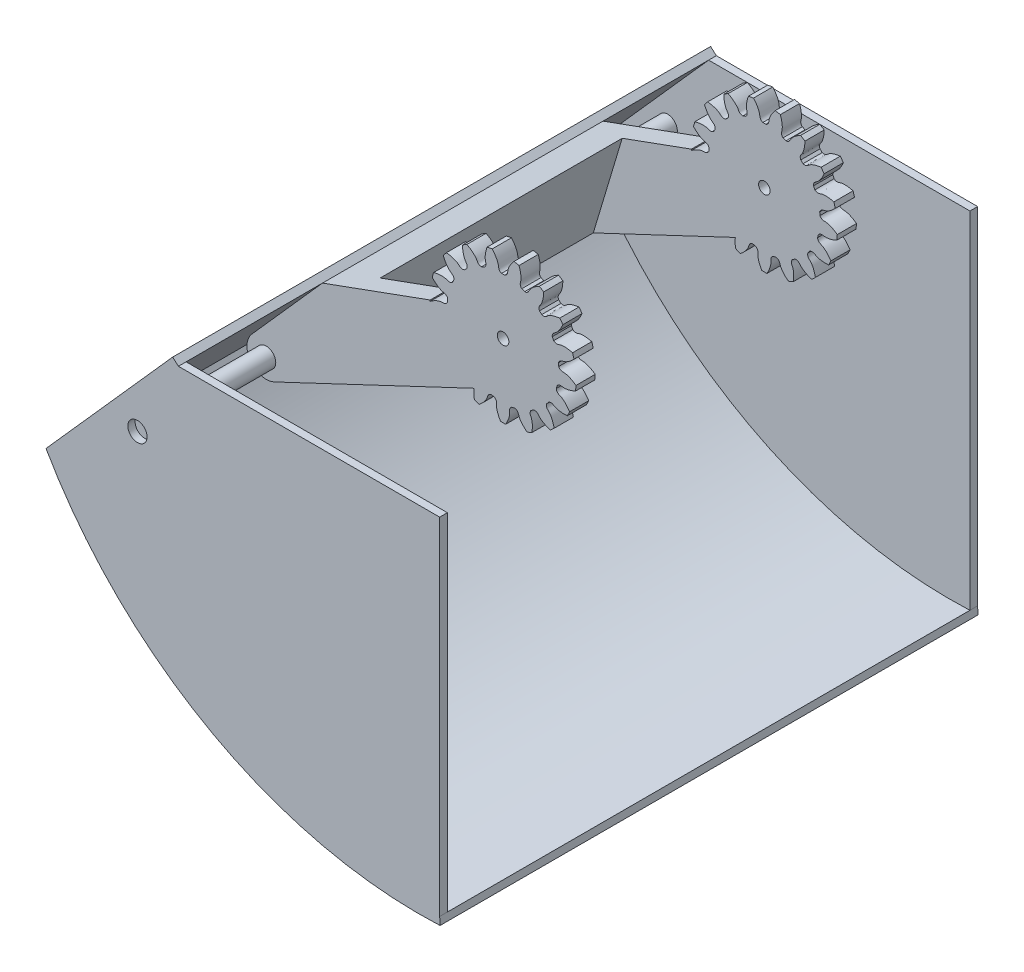
SolidWorks part; units mm, degrees
note: '?' marks a value the reader was unsure of.
ref_plane "前视基准面" through (0, 0, 0) normal (0, 0, 1) x (1, 0, 0)
ref_plane "上视基准面" through (0, 0, 0) normal (0, 1, 0) x (1, 0, 0)
ref_plane "右视基准面" through (0, 0, 0) normal (1, 0, 0) x (0, 0, -1)
sketch "草图1" plane through (0, 0, 0) normal (0, 0, 1) x (1, 0, 0)
  circle A0 centre (0, 0) radius 19
extrude "凸台-拉伸1" add sketch "草图1" along normal blind 5
ref_axis "基准轴1" through (0, 0, -1.5) along (0, 0, 1)?
sketch "草图2" plane through (0, 0, 0) normal (0, 0, 1) x (1, 0, 0)
  line L0 (0, 0) -> (0, 19) construction
  circle A0 centre (0, 0) radius 19 construction
  arc A1 (0.4034, 14.4944) -> (-0.4034, 14.4944) centre (0, 0) ccw
  arc A2 (6.2313, 21.4814) -> (-6.2313, 21.4814) centre (0, 0) ccw
  spline S0 degree 3 poles (0.4034, 14.4944) (1.2558, 14.8496) (1.1324, 15.5096) (1.2766, 16.1296) (1.29, 16.1823) (1.306, 16.2408) (1.3251, 16.3052) (1.3474, 16.3752) (1.3731, 16.4508) (1.4025, 16.5319) (1.4359, 16.6184) (1.4733, 16.7101) (1.5152, 16.8068) (1.5616, 16.9086) (1.6128, 17.0151) (1.669, 17.1264) (1.7304, 17.2421) (1.7972, 17.3621) (1.8696, 17.4863) (1.9478, 17.6145) (2.032, 17.7465) (2.1224, 17.8821) (2.2191, 18.0211) (2.3223, 18.1634) (2.4322, 18.3086) (2.5489, 18.4566) (2.6727, 18.6072) (2.8035, 18.7601) (2.9417, 18.9152) (3.0873, 19.0722) (3.2404, 19.2308) (3.4012, 19.3908) (3.5698, 19.552) (3.7462, 19.7141) (3.9307, 19.8769) (4.1233, 20.0401) (4.324, 20.2035) (4.533, 20.3667) (4.7503, 20.5295) (4.9761, 20.6917) (5.2103, 20.853) (5.453, 21.0131) (5.7916, 21.2269) (6.0532, 21.3811) (6.2313, 21.4814) knots 0 0 0 0 0.193883 0.199024 0.204851 0.211363 0.21856 0.226443 0.235011 0.244265 0.254205 0.264829 0.27614 0.288136 0.300817 0.314184 0.328236 0.342973 0.358397 0.374505 0.391299 0.408779 0.426944 0.445795 0.465331 0.485552 0.506459 0.528051 0.550329 0.573293 0.596941 0.621276 0.646296 0.672001 0.698392 0.725468 0.753229 0.781677 0.810809 0.840627 0.871131 0.90232 0.934195 1 1 1 1
  spline S1 degree 3 poles (-0.4034, 14.4944) (-1.2558, 14.8496) (-1.1324, 15.5096) (-1.2766, 16.1296) (-1.29, 16.1823) (-1.306, 16.2408) (-1.3251, 16.3052) (-1.3474, 16.3752) (-1.3731, 16.4508) (-1.4025, 16.5319) (-1.4359, 16.6184) (-1.4733, 16.7101) (-1.5152, 16.8068) (-1.5616, 16.9086) (-1.6128, 17.0151) (-1.669, 17.1264) (-1.7304, 17.2421) (-1.7972, 17.3621) (-1.8696, 17.4863) (-1.9478, 17.6145) (-2.032, 17.7465) (-2.1224, 17.8821) (-2.2191, 18.0211) (-2.3223, 18.1634) (-2.4322, 18.3086) (-2.5489, 18.4566) (-2.6727, 18.6072) (-2.8035, 18.7601) (-2.9417, 18.9152) (-3.0873, 19.0722) (-3.2404, 19.2308) (-3.4012, 19.3908) (-3.5698, 19.552) (-3.7462, 19.7141) (-3.9307, 19.8769) (-4.1233, 20.0401) (-4.324, 20.2035) (-4.533, 20.3667) (-4.7503, 20.5295) (-4.9761, 20.6917) (-5.2103, 20.853) (-5.453, 21.0131) (-5.7916, 21.2269) (-6.0532, 21.3811) (-6.2313, 21.4814) knots 0 0 0 0 0.193883 0.199024 0.204851 0.211363 0.21856 0.226443 0.235011 0.244265 0.254205 0.264829 0.27614 0.288136 0.300817 0.314184 0.328236 0.342973 0.358397 0.374505 0.391299 0.408779 0.426944 0.445795 0.465331 0.485552 0.506459 0.528051 0.550329 0.573293 0.596941 0.621276 0.646296 0.672001 0.698392 0.725468 0.753229 0.781677 0.810809 0.840627 0.871131 0.90232 0.934195 1 1 1 1
extrude "切除-拉伸1" cut sketch "草图2" along normal through all
pattern_circular "阵列(圆周)1" count 17 over 360 about axis through (0, 0, -1.5) along (0, 0, 1) of "切除-拉伸1"
sketch "草图3" plane through (0, 0, 0) normal (0, 0, 1) x (1, 0, 0)
  circle A0 centre (0, 0) radius 17 construction
  dimension "Dn" = 34
sketch "草图4" plane through (0, 0, 5) normal (0, 0, 1) x (1, 0, 0)
  circle A0 centre (0, 0) radius 1.5
  dimension "D1" = 3
extrude "切除-拉伸2" cut sketch "草图4" against normal up to next
sketch "草图5" plane through (0, 0, 5) normal (0, 0, 1) x (1, 0, 0)
  line L0 (-18.983, -0.8027) -> (-47, -11)
  line L1 (-47, -11) -> (-81.6624, -50)
  line L2 (-81.6624, -50) -> (-7.5441, -14.9851)
  line L3 (0, 0) -> (0, 43.3356) construction
  line L4 (-47, -11) -> (-47, -47.1311) construction
  arc A0 (-18.9691, -1.0834) -> (-18.8452, -2.4206) centre (0, 0) ccw construction
  arc A1 (-18.983, -0.8027) -> (-18.8452, -2.4206) centre (0, 0) ccw
  arc A34 (-4.8598, 13.6613) -> (-5.6121, 13.3699) centre (0, 0) ccw
  arc A35 (-9.4251, 16.4975) -> (-10.5668, 15.7906) centre (0, 0) ccw
  arc A36 (-9.4667, 10.9832) -> (-10.0629, 10.4397) centre (0, 0) ccw
  arc A37 (-14.7482, 11.9787) -> (-15.5575, 10.9071) centre (0, 0) ccw
  arc A38 (-12.795, 6.8218) -> (-13.1546, 6.0996) centre (0, 0) ccw
  arc A39 (-18.0795, 5.8422) -> (-18.447, 4.5505) centre (0, 0) ccw
  arc A40 (-14.3953, 1.739) -> (-14.4698, 0.9357) centre (0, 0) ccw
  arc A41 (-18.9691, -1.0834) -> (-18.8452, -2.4206) centre (0, 0) ccw
  arc A42 (-14.0515, -3.5786) -> (-13.8307, -4.3546) centre (0, 0) ccw
  arc A43 (-17.2968, -7.8627) -> (-16.6982, -9.0648) centre (0, 0) ccw
  arc A44 (-11.8099, -8.4129) -> (-11.3237, -9.0567) centre (0, 0) ccw
  arc A45 (-13.2884, -13.5801) -> (-12.296, -14.4847) centre (0, 0) ccw
  arc A46 (-7.9733, -12.111) -> (-7.2873, -12.5357) centre (0, 0) ccw
  arc A47 (-7.4854, -17.4634) -> (-6.2332, -17.9485) centre (0, 0) ccw
  arc A48 (-3.0599, -14.1735) -> (-2.2668, -14.3217) centre (0, 0) ccw
  arc A49 (-0.6714, -18.9881) -> (0.6714, -18.9881) centre (0, 0) ccw
  arc A50 (2.2668, -14.3217) -> (3.0599, -14.1735) centre (0, 0) ccw
  arc A51 (6.2332, -17.9485) -> (7.4854, -17.4634) centre (0, 0) ccw
  arc A52 (7.2873, -12.5357) -> (7.9733, -12.111) centre (0, 0) ccw
  arc A53 (12.296, -14.4847) -> (13.2884, -13.5801) centre (0, 0) ccw
  arc A54 (11.3237, -9.0567) -> (11.8099, -8.4129) centre (0, 0) ccw
  arc A55 (16.6982, -9.0648) -> (17.2968, -7.8627) centre (0, 0) ccw
  arc A56 (13.8307, -4.3546) -> (14.0515, -3.5786) centre (0, 0) ccw
  arc A57 (18.8452, -2.4206) -> (18.9691, -1.0834) centre (0, 0) ccw
  arc A58 (14.4698, 0.9357) -> (14.3953, 1.739) centre (0, 0) ccw
  arc A59 (18.447, 4.5505) -> (18.0795, 5.8422) centre (0, 0) ccw
  arc A60 (13.1546, 6.0996) -> (12.795, 6.8218) centre (0, 0) ccw
  arc A61 (15.5575, 10.9071) -> (14.7482, 11.9787) centre (0, 0) ccw
  arc A62 (10.0629, 10.4397) -> (9.4667, 10.9832) centre (0, 0) ccw
  arc A63 (10.5668, 15.7906) -> (9.4251, 16.4975) centre (0, 0) ccw
  arc A64 (5.6121, 13.3699) -> (4.8598, 13.6613) centre (0, 0) ccw
  arc A65 (4.1491, 18.5414) -> (2.8291, 18.7882) centre (0, 0) ccw
  arc A66 (0.4034, 14.4944) -> (-0.4034, 14.4944) centre (0, 0) ccw
  arc A67 (-2.8291, 18.7882) -> (-4.1491, 18.5414) centre (0, 0) ccw
  arc A76 (-14.0515, -3.5786) -> (-13.8307, -4.3546) centre (0, 0) ccw
  arc A77 (-17.2968, -7.8627) -> (-16.6982, -9.0648) centre (0, 0) ccw
  arc A78 (-11.8099, -8.4129) -> (-11.3237, -9.0567) centre (0, 0) ccw
  arc A79 (-13.2884, -13.5801) -> (-12.296, -14.4847) centre (0, 0) ccw
  arc A80 (-7.9733, -12.111) -> (-7.2873, -12.5357) centre (0, 0) ccw
  spline S1 degree 3 poles (-7.4854, -17.4634) (-7.5096, -17.32) (-7.5487, -17.0538) (-7.5886, -16.6719) (-7.6106, -16.3274) (-7.6183, -16.008) (-7.6136, -15.714) (-7.5986, -15.446) (-7.5788, -15.2392) (-7.5553, -15.0543) (-7.5342, -14.9196) (-7.5105, -14.7941) (-7.4928, -14.7096) (-7.4749, -14.6318) (-7.4569, -14.5605) (-7.4345, -14.4783) (-7.4122, -14.4049) (-7.202, -13.7827) (-6.7497, -13.2865) (-7.2873, -12.5357) knots 0.467653 0.467653 0.467653 0.467653 0.514448 0.554205 0.591221 0.625495 0.657027 0.685816 0.711864 0.72386 0.745795 0.755735 0.764989 0.773557 0.78144 0.788637 0.800976 0.806117 1 1 1 1 construction
  spline S36 degree 3 poles (801.6528, 603.553) (-19.7252, -7.542) (-3.7936, 9.8487) (-7.0285, 14.596) (-7.0736, 14.658) (-7.1257, 14.7254) (-7.1718, 14.7827) (-7.243, 14.8676) (-7.3458, 14.9828) (-7.4879, 15.1299) (-7.6543, 15.2888) (-7.8461, 15.4578) (-8.0643, 15.6352) (-8.3098, 15.8191) (-8.5836, 16.0075) (-8.8863, 16.1985) (-30.7559, 28.8047) (-98.5587, -42.3055) (899.0002, 434.536) knots -1.169641 -1.169641 -1.169641 -1.169641 0.661536 0.666677 0.679016 0.686213 0.694096 0.702664 0.721858 0.743793 0.76847 0.795889 0.82605 0.858952 0.894597 0.932984 0.974112 9.016656 9.016656 9.016656 9.016656 only from (-5.6121, 13.3699) to (-9.4251, 16.4975)
  spline S37 degree 3 poles (-789.8845, -610.8384) (79.969, 69.9323) (-12.5204, 39.6369) (-10.5228, 14.9936) (-10.4812, 14.651) (-10.43, 14.3355) (-10.3714, 14.0475) (-10.3075, 13.7868) (-10.25, 13.5872) (-10.1929, 13.4097) (-10.1474, 13.2812) (-10.101, 13.1621) (-10.0681, 13.0824) (-10.0362, 13.0091) (-10.0055, 12.9424) (-9.9683, 12.8657) (-9.9329, 12.7977) (-7.1253, 7.786) (15.5424, 14.2951) (-897.5321, -448.5461) knots -7.831656 -7.831656 -7.831656 -7.831656 0.046795 0.086552 0.123568 0.157842 0.189373 0.218163 0.244211 0.256207 0.278142 0.288082 0.297336 0.305904 0.313787 0.320984 0.333323 0.338464 2.169591 2.169591 2.169591 2.169591 only from (-10.5668, 15.7906) to (-9.4667, 10.9832)
  spline S38 degree 3 poles (529.4905, 852.3868) (-15.6687, -14.1583) (-7.0952, 7.8132) (-11.8266, 11.0714) (-11.8911, 11.1129) (-11.964, 11.157) (-12.0276, 11.1937) (-12.1246, 11.2471) (-12.2622, 11.3174) (-12.4478, 11.4032) (-12.6604, 11.4913) (-12.9003, 11.5797) (-13.1678, 11.6663) (-13.4632, 11.749) (-13.7866, 11.8258) (-14.1378, 11.8946) (-39.0844, 15.7493) (-76.6207, -75.0522) (681.3202, 729.9491) knots -1.169641 -1.169641 -1.169641 -1.169641 0.661536 0.666677 0.679016 0.686213 0.694096 0.702664 0.721858 0.743793 0.76847 0.795889 0.82605 0.858952 0.894597 0.932984 0.974112 9.016656 9.016656 9.016656 9.016656 only from (-10.0629, 10.4397) to (-14.7482, 11.9787)
  spline S39 degree 3 poles (-515.8851, -854.929) (49.3064, 94.0981) (-25.9934, 32.4374) (-15.2285, 10.1798) (-15.066, 9.8754) (-14.9043, 9.5997) (-14.7456, 9.3523) (-14.5918, 9.1323) (-14.466, 8.9669) (-14.3487, 8.8221) (-14.2599, 8.7187) (-14.1736, 8.6244) (-14.1141, 8.5619) (-14.0579, 8.5052) (-14.0051, 8.454) (-13.9428, 8.3959) (-13.8852, 8.3453) (-9.4567, 4.6863) (9.3288, 18.9444) (-674.8902, -742.4828) knots -7.831656 -7.831656 -7.831656 -7.831656 0.046795 0.086552 0.123568 0.157842 0.189373 0.218163 0.244211 0.256207 0.278142 0.288082 0.297336 0.305904 0.313787 0.320984 0.333323 0.338464 2.169591 2.169591 2.169591 2.169591 only from (-15.5575, 10.9071) to (-12.795, 6.8218)
  spline S40 degree 3 poles (185.8176, 986.101) (-9.496, -18.8624) (-9.4385, 4.7225) (-15.0274, 6.0515) (-15.1025, 6.0669) (-15.1864, 6.0817) (-15.2591, 6.0929) (-15.3688, 6.1077) (-15.5225, 6.1236) (-15.7266, 6.1365) (-15.9566, 6.1418) (-16.2122, 6.1376) (-16.493, 6.1217) (-16.7983, 6.0922) (-17.1276, 6.047) (-17.4799, 5.9842) (-42.1345, 0.5668) (-44.3347, -97.6627) (371.6241, 926.7785) knots -1.169641 -1.169641 -1.169641 -1.169641 0.661536 0.666677 0.679016 0.686213 0.694096 0.702664 0.721858 0.743793 0.76847 0.795889 0.82605 0.858952 0.894597 0.932984 0.974112 9.016656 9.016656 9.016656 9.016656 only from (-13.1546, 6.0996) to (-18.0795, 5.8422)
  spline S41 degree 3 poles (-172.2126, -983.5568) (11.9847, 105.5554) (-35.9559, 20.8571) (-17.8776, 3.9912) (-17.616, 3.7661) (-17.3657, 3.5674) (-17.1283, 3.394) (-16.9054, 3.2444) (-16.7284, 3.1357) (-16.5667, 3.043) (-16.4465, 2.9787) (-16.332, 2.9219) (-16.2539, 2.8852) (-16.181, 2.8525) (-16.1134, 2.8239) (-16.0342, 2.7923) (-15.9623, 2.7658) (-10.511, 0.9536) (1.8554, 21.035) (-361.1007, -936.143) knots -7.831656 -7.831656 -7.831656 -7.831656 0.046795 0.086552 0.123568 0.157842 0.189373 0.218163 0.244211 0.256207 0.278142 0.288082 0.297336 0.305904 0.313787 0.320984 0.333323 0.338464 2.169591 2.169591 2.169591 2.169591 only from (-18.447, 4.5505) to (-14.3953, 1.739)
  spline S42 degree 3 poles (-182.9511, 986.6369) (-2.0409, -21.019) (-10.5071, 0.994) (-16.1987, 0.2143) (-16.2743, 0.2016) (-16.3579, 0.185) (-16.4297, 0.1693) (-16.5374, 0.1434) (-16.6864, 0.1027) (-16.8814, 0.041) (-17.0978, -0.0371) (-17.3346, -0.1334) (-17.5907, -0.2496) (-17.8647, -0.3875) (-18.1554, -0.5486) (-18.4613, -0.7344) (-39.494, -14.6922) (-6.061, -107.0833) (11.7382, 998.4413) knots -1.169641 -1.169641 -1.169641 -1.169641 0.661536 0.666677 0.679016 0.686213 0.694096 0.702664 0.721858 0.743793 0.76847 0.795889 0.82605 0.858952 0.894597 0.932984 0.974112 9.016656 9.016656 9.016656 9.016656 only from (-14.4698, 0.9357) to (-18.9691, -1.0834)
  spline S43 degree 3 poles (755.9193, -3926.2535) (-1.4249, 230.148) (-53.2365, 11.3382) (-18.1121, -2.7364) (-17.7869, -2.8519) (-17.4817, -2.9467) (-17.1977, -3.0226) (-16.9358, -3.0816) (-16.7315, -3.1191) (-16.5473, -3.147) (-16.4119, -3.1636) (-16.2846, -3.1752) (-16.1986, -3.1813) (-16.1188, -3.1853) (-16.0454, -3.1876) (-15.9602, -3.1885) (-15.8835, -3.1872) (-6.8836, -2.7489) (-1.4385, 54.3405) (17.9437, -4002.7644) knots -12.051564 -12.051564 -12.051564 -12.051564 0.046795 0.086552 0.123568 0.157842 0.189373 0.218163 0.244211 0.256207 0.278142 0.288082 0.297336 0.305904 0.313787 0.320984 0.333323 0.338464 3.220589 3.220589 3.220589 3.220589 only from (-18.8452, -2.4206) to (-14.0515, -3.5786)
  spline S44 degree 3 poles (-2091.9835, 3412.7558) (27.3841, -46.9593) (-7.2996, -1.2865) (-15.1823, -5.6518) (-15.2482, -5.691) (-15.3201, -5.7366) (-15.3814, -5.7772) (-15.4724, -5.8403) (-15.5967, -5.932) (-15.7562, -6.06) (-15.9298, -6.211) (-16.1158, -6.3864) (-16.3126, -6.5872) (-16.5184, -6.8148) (-16.7313, -7.07) (-16.9493, -7.3538) (-39.2418, -38.8919) (124.1972, -196.1218) (-1429.0442, 3734.2026) knots -2.220614 -2.220614 -2.220614 -2.220614 0.661536 0.666677 0.679016 0.686213 0.694096 0.702664 0.721858 0.743793 0.76847 0.795889 0.82605 0.858952 0.894597 0.932984 0.974112 13.321347 13.321347 13.321347 13.321347 only from (-13.8307, -4.3546) to (-17.2968, -7.8627)
  spline S45 degree 3 poles (2123.2001, -3388.0528) (-84.4678, 214.0919) (-53.7373, -8.6587) (-15.9006, -9.0945) (-15.5556, -9.0847) (-15.2368, -9.0628) (-14.9445, -9.031) (-14.679, -8.9914) (-14.4749, -8.9526) (-14.293, -8.9121) (-14.1608, -8.8786) (-14.038, -8.8435) (-13.9555, -8.8181) (-13.8797, -8.793) (-13.8104, -8.7686) (-13.7306, -8.7387) (-13.6596, -8.7097) (-5.4257, -5.05) (-20.9714, 50.1513) (1462.6972, -3725.9846) knots -12.051564 -12.051564 -12.051564 -12.051564 0.046795 0.086552 0.123568 0.157842 0.189373 0.218163 0.244211 0.256207 0.278142 0.288082 0.297336 0.305904 0.313787 0.320984 0.333323 0.338464 3.220589 3.220589 3.220589 3.220589 only from (-16.6982, -9.0648) to (-11.8099, -8.4129)
  spline S46 degree 3 poles (-3183.5461, 2426.5884) (42.4986, -33.896) (-6.342, -3.8366) (-12.1154, -10.7546) (-12.1627, -10.815) (-12.2133, -10.8835) (-12.2557, -10.9435) (-12.3179, -11.0352) (-12.4006, -11.1656) (-12.5031, -11.3426) (-12.6104, -11.5461) (-12.7206, -11.7768) (-12.8315, -12.0352) (-12.9411, -12.3217) (-13.0474, -12.6366) (-13.1483, -12.98) (-22.5426, -50.4414) (186.6578, -138.0129) (-2681.4936, 2965.8099) knots -2.220614 -2.220614 -2.220614 -2.220614 0.661536 0.666677 0.679016 0.686213 0.694096 0.702664 0.721858 0.743793 0.76847 0.795889 0.82605 0.858952 0.894597 0.932984 0.974112 13.321347 13.321347 13.321347 13.321347 only from (-11.3237, -9.0567) to (-13.2884, -13.5801)
  spline S47 degree 3 poles (3203.731, -2392.2768) (-156.1027, 169.1214) (-46.9807, -27.4862) (-11.5415, -14.2243) (-11.2234, -14.0905) (-10.934, -13.955) (-10.6729, -13.8198) (-10.4397, -13.6869) (-10.2635, -13.577) (-10.1084, -13.4735) (-9.9973, -13.3946) (-9.8954, -13.3174) (-9.8277, -13.2639) (-9.766, -13.2132) (-9.7102, -13.1654) (-9.6466, -13.1086) (-9.5908, -13.056) (-3.2351, -6.6689) (-37.672, 39.1889) (2709.9054, -2945.99) knots -12.051564 -12.051564 -12.051564 -12.051564 0.046795 0.086552 0.123568 0.157842 0.189373 0.218163 0.244211 0.256207 0.278142 0.288082 0.297336 0.305904 0.313787 0.320984 0.333323 0.338464 3.220589 3.220589 3.220589 3.220589 only from (-12.296, -14.4847) to (-7.9733, -12.111)
  spline S48 degree 3 poles (-3845.1532, 1112.6968) (51.8734, -16.2548) (-4.5278, -5.8685) (-7.4122, -14.4049) (-7.4345, -14.4783) (-7.4569, -14.5605) (-7.4749, -14.6318) (-7.4997, -14.7397) (-7.5297, -14.8912) (-7.5614, -15.0933) (-7.5879, -15.3218) (-7.6073, -15.5767) (-7.6174, -15.8578) (-7.6161, -16.1645) (-7.6015, -16.4966) (-7.5715, -16.8532) (-2.7988, -55.1785) (223.9092, -61.2646) (-3571.7924, 1796.8681) knots -2.220614 -2.220614 -2.220614 -2.220614 0.661536 0.666677 0.679016 0.686213 0.694096 0.702664 0.721858 0.743793 0.76847 0.795889 0.82605 0.858952 0.894597 0.932984 0.974112 13.321347 13.321347 13.321347 13.321347 only from (-7.2873, -12.5357) to (-7.4854, -17.4634)
  spline S49 degree 3 poles (963.4713, -262.2291) (-103.9993, 21.673) (-24.0857, -33.8781) (-5.6237, -17.433) (-5.3754, -17.1934) (-5.1545, -16.9624) (-4.9599, -16.7421) (-4.7904, -16.5339) (-4.6658, -16.3677) (-4.5586, -16.2153) (-4.4835, -16.1015) (-4.4164, -15.9927) (-4.3726, -15.9184) (-4.3334, -15.8488) (-4.2986, -15.7841) (-4.2598, -15.7082) (-4.2268, -15.639) (-1.9194, -10.3782) (-20.7741, 3.7883) (898.8314, -445.9367) knots -7.831656 -7.831656 -7.831656 -7.831656 0.046795 0.086552 0.123568 0.157842 0.189373 0.218163 0.244211 0.256207 0.278142 0.288082 0.297336 0.305904 0.313787 0.320984 0.333323 0.338464 2.169591 2.169591 2.169591 2.169591 only from (-6.2332, -17.9485) to (-3.0599, -14.1735)
  spline S50 degree 3 poles (-999.3086, -91.1352) (20.741, -3.9716) (-1.9593, -10.3706) (-1.7081, -16.1098) (-1.7023, -16.1863) (-1.6935, -16.271) (-1.6845, -16.344) (-1.6687, -16.4536) (-1.6419, -16.6057) (-1.5985, -16.8056) (-1.5407, -17.0283) (-1.4666, -17.273) (-1.3745, -17.5386) (-1.2625, -17.8243) (-1.129, -18.1286) (-0.9721, -18.4503) (10.9855, -40.6811) (106.0673, -15.9155) (-993.0991, 103.8126) knots -1.169641 -1.169641 -1.169641 -1.169641 0.661536 0.666677 0.679016 0.686213 0.694096 0.702664 0.721858 0.743793 0.76847 0.795889 0.82605 0.858952 0.894597 0.932984 0.974112 9.016656 9.016656 9.016656 9.016656 only from (-2.2668, -14.3217) to (-0.6714, -18.9881)
  spline S51 degree 3 poles (993.1383, 103.5246) (-104.8057, -17.3594) (-10.2211, -40.2911) (1.0535, -18.2873) (1.1985, -17.9742) (1.3211, -17.679) (1.4229, -17.4032) (1.5058, -17.1479) (1.562, -16.9479) (1.6068, -16.767) (1.6358, -16.6338) (1.6591, -16.5081) (1.6731, -16.423) (1.6845, -16.344) (1.6935, -16.271) (1.7023, -16.1863) (1.7081, -16.1098) (1.9593, -10.3707) (-20.7398, -3.9719) (999.2263, -91.1282) knots -7.831656 -7.831656 -7.831656 -7.831656 0.046795 0.086552 0.123568 0.157842 0.189373 0.218163 0.244211 0.256207 0.278142 0.288082 0.297336 0.305904 0.313787 0.320984 0.333323 0.338464 2.169591 2.169591 2.169591 2.169591 only from (0.6714, -18.9881) to (2.2668, -14.3217)
  spline S52 degree 3 poles (-898.9057, -445.973) (20.7751, 3.7891) (1.9193, -10.3781) (4.2268, -15.639) (4.2598, -15.7082) (4.2986, -15.7841) (4.3334, -15.8488) (4.3877, -15.9453) (4.4676, -16.0775) (4.5803, -16.2481) (4.7147, -16.4349) (4.8721, -16.6364) (5.054, -16.8508) (5.2616, -17.0767) (5.4961, -17.3122) (5.7585, -17.5556) (24.9393, -33.9656) (104.6541, 23.4751) (-963.5388, -261.9464) knots -1.169641 -1.169641 -1.169641 -1.169641 0.661536 0.666677 0.679016 0.686213 0.694096 0.702664 0.721858 0.743793 0.76847 0.795889 0.82605 0.858952 0.894597 0.932984 0.974112 9.016656 9.016656 9.016656 9.016656 only from (3.0599, -14.1735) to (6.2332, -17.9485)
  spline S53 degree 3 poles (888.6765, 455.2968) (-91.4574, -54.0473) (5.0239, -41.2626) (7.5886, -16.6719) (7.6106, -16.3274) (7.6183, -16.008) (7.6136, -15.714) (7.5986, -15.446) (7.5788, -15.2392) (7.5553, -15.0543) (7.5342, -14.9196) (7.5105, -14.7941) (7.4928, -14.7096) (7.4749, -14.6318) (7.4569, -14.5605) (7.4345, -14.4783) (7.4122, -14.4049) (5.5733, -8.9627) (-17.9045, -11.1958) (964.67, 275.9876) knots -7.831656 -7.831656 -7.831656 -7.831656 0.046795 0.086552 0.123568 0.157842 0.189373 0.218163 0.244211 0.256207 0.278142 0.288082 0.297336 0.305904 0.313787 0.320984 0.333323 0.338464 2.169591 2.169591 2.169591 2.169591 only from (7.4854, -17.4634) to (7.2873, -12.5357)
  spline S54 degree 3 poles (-677.1006, -740.5796) (18.0035, 11.0381) (5.5387, -8.9839) (9.5908, -13.056) (9.6466, -13.1086) (9.7102, -13.1654) (9.766, -13.2132) (9.8515, -13.2835) (9.9738, -13.3779) (10.1406, -13.4963) (10.3333, -13.622) (10.5529, -13.7529) (10.7999, -13.8872) (11.0751, -14.0228) (11.3788, -14.1577) (11.7115, -14.2899) (35.525, -22.6629) (89.1069, 59.6953) (-803.8472, -592.3281) knots -1.169641 -1.169641 -1.169641 -1.169641 0.661536 0.666677 0.679016 0.686213 0.694096 0.702664 0.721858 0.743793 0.76847 0.795889 0.82605 0.858952 0.894597 0.932984 0.974112 9.016656 9.016656 9.016656 9.016656 only from (7.9733, -12.111) to (12.296, -14.4847)
  spline S55 degree 3 poles (664.194, 745.5786) (-65.7574, -83.4359) (19.5905, -36.6614) (13.0987, -12.8047) (12.9948, -12.4756) (12.8866, -12.1749) (12.776, -11.9025) (12.6653, -11.658) (12.5721, -11.4724) (12.4833, -11.3085) (12.415, -11.1905) (12.3475, -11.082) (12.3005, -11.0096) (12.2557, -10.9435) (12.2133, -10.8835) (12.1627, -10.815) (12.1154, -10.7546) (8.4346, -6.3441) (-12.651, -16.9076) (799.8298, 605.8298) knots -7.831656 -7.831656 -7.831656 -7.831656 0.046795 0.086552 0.123568 0.157842 0.189373 0.218163 0.244211 0.256207 0.278142 0.288082 0.297336 0.305904 0.313787 0.320984 0.333323 0.338464 2.169591 2.169591 2.169591 2.169591 only from (13.2884, -13.5801) to (11.3237, -9.0567)
  spline S56 degree 3 poles (-363.8493, -935.1669) (12.8003, 16.7963) (8.4101, -6.3764) (13.6596, -8.7097) (13.7306, -8.7387) (13.8104, -8.7686) (13.8797, -8.793) (13.9849, -8.8277) (14.133, -8.8716) (14.3312, -8.9218) (14.5563, -8.9693) (14.8084, -9.0121) (15.0873, -9.048) (15.3929, -9.0751) (15.7248, -9.0912) (16.0827, -9.0942) (41.3129, -8.2994) (61.5253, 87.8533) (-535.5916, -842.7126) knots -1.169641 -1.169641 -1.169641 -1.169641 0.661536 0.666677 0.679016 0.686213 0.694096 0.702664 0.721858 0.743793 0.76847 0.795889 0.82605 0.858952 0.894597 0.932984 0.974112 9.016656 9.016656 9.016656 9.016656 only from (11.8099, -8.4129) to (16.6982, -9.0648)
  spline S57 degree 3 poles (350.0084, 935.1659) (-31.1764, -101.5559) (31.5112, -27.1089) (16.8398, -7.2083) (16.624, -6.9389) (16.4145, -6.6976) (16.213, -6.4835) (16.0214, -6.2956) (15.8674, -6.1561) (15.7255, -6.0353) (15.6191, -5.95) (15.517, -5.8732) (15.447, -5.8227) (15.3814, -5.7772) (15.3201, -5.7366) (15.2482, -5.691) (15.1823, -5.6518) (10.1568, -2.8688) (-5.689, -20.336) (526.9681, 853.8513) knots -7.831656 -7.831656 -7.831656 -7.831656 0.046795 0.086552 0.123568 0.157842 0.189373 0.218163 0.244211 0.256207 0.278142 0.288082 0.297336 0.305904 0.313787 0.320984 0.333323 0.338464 2.169591 2.169591 2.169591 2.169591 only from (17.2968, -7.8627) to (13.8307, -4.3546)
  spline S58 degree 3 poles (-1.4581, -1003.4547) (5.8684, 20.2861) (10.1456, -2.9078) (15.8835, -3.1872) (15.9602, -3.1885) (16.0454, -3.1876) (16.1188, -3.1853) (16.2294, -3.1797) (16.3834, -3.1671) (16.5864, -3.1423) (16.8135, -3.1053) (17.0639, -3.0541) (17.337, -2.9869) (17.6317, -2.9017) (17.9471, -2.7968) (18.2819, -2.6704) (41.5212, 7.185) (25.6343, 104.1463) (-195.0014, -979.2841) knots -1.169641 -1.169641 -1.169641 -1.169641 0.661536 0.666677 0.679016 0.686213 0.694096 0.702664 0.721858 0.743793 0.76847 0.795889 0.82605 0.858952 0.894597 0.932984 0.974112 9.016656 9.016656 9.016656 9.016656 only from (14.0515, -3.5786) to (18.8452, -2.4206)
  spline S59 degree 3 poles (-11.4478, 998.4538) (7.6151, -105.9603) (39.1762, -13.8951) (18.3065, -0.6383) (18.0081, -0.465) (17.7255, -0.3157) (17.4603, -0.1889) (17.2137, -0.0828) (17.0198, -0.0085) (16.8438, 0.0529) (16.7138, 0.094) (16.5908, 0.1288) (16.5073, 0.1506) (16.4297, 0.1693) (16.3579, 0.185) (16.2743, 0.2016) (16.1987, 0.2143) (10.5073, 0.994) (2.0414, -21.0178) (182.9364, 986.5555) knots -7.831656 -7.831656 -7.831656 -7.831656 0.046795 0.086552 0.123568 0.157842 0.189373 0.218163 0.244211 0.256207 0.278142 0.288082 0.297336 0.305904 0.313787 0.320984 0.333323 0.338464 2.169591 2.169591 2.169591 2.169591 only from (18.9691, -1.0834) to (14.4698, 0.9357)
  spline S60 degree 3 poles (361.13, -936.2203) (-1.8561, 21.0361) (10.5109, 0.9536) (15.9623, 2.7658) (16.0342, 2.7923) (16.1134, 2.8239) (16.181, 2.8525) (16.2821, 2.8978) (16.4211, 2.9651) (16.6015, 3.0616) (16.7998, 3.1782) (17.0149, 3.3163) (17.2453, 3.4776) (17.4893, 3.6635) (17.7455, 3.8753) (18.012, 4.1141) (36.1218, 21.699) (-13.7187, 106.3737) (171.9248, -983.5979) knots -1.169641 -1.169641 -1.169641 -1.169641 0.661536 0.666677 0.679016 0.686213 0.694096 0.702664 0.721858 0.743793 0.76847 0.795889 0.82605 0.858952 0.894597 0.932984 0.974112 9.016656 9.016656 9.016656 9.016656 only from (14.3953, 1.739) to (18.447, 4.5505)
  spline S61 degree 3 poles (-371.3578, 926.8951) (45.3782, -96.0541) (41.5502, 1.1953) (17.3009, 6.0179) (16.96, 6.0716) (16.6426, 6.1088) (16.3495, 6.1312) (16.0812, 6.1411) (15.8735, 6.1404) (15.6872, 6.134) (15.5512, 6.1254) (15.4239, 6.1134) (15.3382, 6.1036) (15.2591, 6.0929) (15.1864, 6.0817) (15.1025, 6.0669) (15.0274, 6.0515) (9.4387, 4.7226) (9.496, -18.8611) (-185.8018, 986.0199) knots -7.831656 -7.831656 -7.831656 -7.831656 0.046795 0.086552 0.123568 0.157842 0.189373 0.218163 0.244211 0.256207 0.278142 0.288082 0.297336 0.305904 0.313787 0.320984 0.333323 0.338464 2.169591 2.169591 2.169591 2.169591 only from (18.0795, 5.8422) to (13.1546, 6.0996)
  spline S62 degree 3 poles (674.9455, -742.5443) (-9.3298, 18.9451) (9.4566, 4.6862) (13.8852, 8.3453) (13.9428, 8.3959) (14.0051, 8.454) (14.0579, 8.5052) (14.1359, 8.5839) (14.2411, 8.6969) (14.3744, 8.852) (14.5173, 9.0323) (14.6679, 9.2389) (14.8245, 9.4725) (14.9849, 9.734) (15.1473, 10.024) (15.3095, 10.343) (25.844, 33.2824) (-51.2189, 94.2348) (515.6317, -855.0713) knots -1.169641 -1.169641 -1.169641 -1.169641 0.661536 0.666677 0.679016 0.686213 0.694096 0.702664 0.721858 0.743793 0.76847 0.795889 0.82605 0.858952 0.894597 0.932984 0.974112 9.016656 9.016656 9.016656 9.016656 only from (12.795, 6.8218) to (15.5575, 10.9071)
  spline S63 degree 3 poles (-681.114, 730.154) (77.0126, -73.1753) (38.3126, 16.1242) (13.9587, 11.8613) (13.6214, 11.7883) (13.312, 11.7083) (13.0306, 11.6233) (12.7769, 11.5356) (12.5835, 11.4599) (12.4121, 11.3867) (12.2883, 11.3295) (12.174, 11.2723) (12.0976, 11.2322) (12.0276, 11.1937) (11.964, 11.157) (11.8911, 11.1129) (11.8266, 11.0714) (7.0953, 7.8133) (15.6682, -14.1571) (-529.4465, 852.3168) knots -7.831656 -7.831656 -7.831656 -7.831656 0.046795 0.086552 0.123568 0.157842 0.189373 0.218163 0.244211 0.256207 0.278142 0.288082 0.297336 0.305904 0.313787 0.320984 0.333323 0.338464 2.169591 2.169591 2.169591 2.169591 only from (14.7482, 11.9787) to (10.0629, 10.4397)
  spline S64 degree 3 poles (897.6059, -448.5835) (-15.5436, 14.2955) (7.1252, 7.7858) (9.9329, 12.7977) (9.9683, 12.8657) (10.0055, 12.9424) (10.0362, 13.0091) (10.0804, 13.1107) (10.1378, 13.2541) (10.206, 13.4469) (10.2741, 13.6667) (10.34, 13.9137) (10.4015, 14.1881) (10.4567, 14.4899) (10.5033, 14.8189) (10.5394, 15.175) (12.0758, 40.3709) (-81.8017, 69.3689) (789.6996, -611.0626) knots -1.169641 -1.169641 -1.169641 -1.169641 0.661536 0.666677 0.679016 0.686213 0.694096 0.702664 0.721858 0.743793 0.76847 0.795889 0.82605 0.858952 0.894597 0.932984 0.974112 9.016656 9.016656 9.016656 9.016656 only from (9.4667, 10.9832) to (10.5668, 15.7906)
  spline S65 degree 3 poles (-898.8819, 434.8016) (98.2461, -40.4138) (29.9007, 28.8755) (8.7313, 16.1028) (8.4432, 15.9129) (8.1836, 15.7265) (7.9518, 15.5456) (7.747, 15.3721) (7.5939, 15.2317) (7.4606, 15.1015) (7.3658, 15.0035) (7.2798, 14.9089) (7.2231, 14.8439) (7.1718, 14.7827) (7.1257, 14.7254) (7.0736, 14.658) (7.0285, 14.596) (3.7937, 9.8488) (19.7243, -7.5411) (-801.5865, 603.5036) knots -7.831656 -7.831656 -7.831656 -7.831656 0.046795 0.086552 0.123568 0.157842 0.189373 0.218163 0.244211 0.256207 0.278142 0.288082 0.297336 0.305904 0.313787 0.320984 0.333323 0.338464 2.169591 2.169591 2.169591 2.169591 only from (9.4251, 16.4975) to (5.6121, 13.3699)
  spline S66 degree 3 poles (999.0396, -94.039) (-19.6581, 7.7151) (3.8315, 9.834) (4.6391, 15.5216) (4.6476, 15.5979) (4.6545, 15.6828) (4.659, 15.7561) (4.6636, 15.8668) (4.6652, 16.0213) (4.6593, 16.2257) (4.6434, 16.4552) (4.6155, 16.7094) (4.5738, 16.9875) (4.5162, 17.2888) (4.4408, 17.6125) (4.3458, 17.9575) (-3.3233, 42.007) (-101.3368, 35.1344) (957.1142, -284.5265) knots -1.169641 -1.169641 -1.169641 -1.169641 0.661536 0.666677 0.679016 0.686213 0.694096 0.702664 0.721858 0.743793 0.76847 0.795889 0.82605 0.858952 0.894597 0.932984 0.974112 9.016656 9.016656 9.016656 9.016656 only from (4.8598, 13.6613) to (4.1491, 18.5414)
  spline S67 degree 3 poles (-995.2509, 80.7268) (106.2109, -2.1942) (17.4505, 37.727) (2.3247, 18.1696) (2.1246, 17.8883) (1.9499, 17.6208) (1.7991, 17.3684) (1.6708, 17.1326) (1.5788, 16.9464) (1.5015, 16.7768) (1.4485, 16.6512) (1.4025, 16.5319) (1.3731, 16.4508) (1.3474, 16.3752) (1.3251, 16.3052) (1.3009, 16.2235) (1.2812, 16.1494) (-0.0203, 10.5542) (21.1165, 0.0934) (-965.4678, 273.1839) knots -7.831656 -7.831656 -7.831656 -7.831656 0.046795 0.086552 0.123568 0.157842 0.189373 0.218163 0.244211 0.256207 0.278142 0.288082 0.297336 0.305904 0.313787 0.320984 0.333323 0.338464 2.169591 2.169591 2.169591 2.169591 only from (2.8291, 18.7882) to (0.4034, 14.4944)
  spline S68 degree 3 poles (965.5475, 273.206) (-21.1176, 0.0928) (0.0203, 10.554) (-1.2812, 16.1494) (-1.3009, 16.2235) (-1.3251, 16.3052) (-1.3474, 16.3752) (-1.3831, 16.4801) (-1.4373, 16.6247) (-1.5168, 16.8131) (-1.6145, 17.0214) (-1.7323, 17.2483) (-1.8716, 17.4926) (-2.0342, 17.7528) (-2.2214, 18.0273) (-2.4347, 18.3148) (-18.2735, 37.9699) (-107.1857, -3.8453) (995.2652, 80.4365) knots -1.169641 -1.169641 -1.169641 -1.169641 0.661536 0.666677 0.679016 0.686213 0.694096 0.702664 0.721858 0.743793 0.76847 0.795889 0.82605 0.858952 0.894597 0.932984 0.974112 9.016656 9.016656 9.016656 9.016656 only from (-0.4034, 14.4944) to (-2.8291, 18.7882)
  spline S69 degree 3 poles (-957.2057, -284.2506) (99.8314, 36.3218) (2.6436, 41.4832) (-4.3959, 17.7824) (-4.4809, 17.4479) (-4.5471, 17.1353) (-4.5965, 16.8455) (-4.6311, 16.5793) (-4.6495, 16.3724) (-4.6604, 16.1863) (-4.6644, 16.05) (-4.6642, 15.9222) (-4.6623, 15.836) (-4.659, 15.7561) (-4.6545, 15.6828) (-4.6476, 15.5979) (-4.6391, 15.5216) (-3.8315, 9.8342) (19.6568, 7.7152) (-998.9573, -94.0308) knots -7.831656 -7.831656 -7.831656 -7.831656 0.046795 0.086552 0.123568 0.157842 0.189373 0.218163 0.244211 0.256207 0.278142 0.288082 0.297336 0.305904 0.313787 0.320984 0.333323 0.338464 2.169591 2.169591 2.169591 2.169591 only from (-4.1491, 18.5414) to (-4.8598, 13.6613)
  spline S77 degree 3 poles (-18.8452, -2.4206) (-18.7139, -2.4831) (-18.4686, -2.5936) (-18.1121, -2.7364) (-17.7869, -2.8519) (-17.4817, -2.9467) (-17.1977, -3.0226) (-16.9358, -3.0816) (-16.7315, -3.1191) (-16.5473, -3.147) (-16.4119, -3.1636) (-16.2846, -3.1752) (-16.1986, -3.1813) (-16.1188, -3.1853) (-16.0454, -3.1876) (-15.9602, -3.1885) (-15.8835, -3.1872) (-15.2275, -3.1552) (-14.6264, -2.856) (-14.0515, -3.5786) knots 0 0 0 0 0.046795 0.086552 0.123568 0.157842 0.189373 0.218163 0.244211 0.256207 0.278142 0.288082 0.297336 0.305904 0.313787 0.320984 0.333323 0.338464 0.532347 0.532347 0.532347 0.532347
  spline S78 degree 3 poles (-13.8307, -4.3546) (-13.9391, -5.2716) (-14.6077, -5.3336) (-15.1823, -5.6518) (-15.2482, -5.691) (-15.3201, -5.7366) (-15.3814, -5.7772) (-15.4724, -5.8403) (-15.5967, -5.932) (-15.7562, -6.06) (-15.9298, -6.211) (-16.1158, -6.3864) (-16.3126, -6.5872) (-16.5184, -6.8148) (-16.7313, -7.07) (-16.9493, -7.3538) (-17.1384, -7.6213) (-17.2532, -7.7951) (-17.2968, -7.8627) knots 0.467653 0.467653 0.467653 0.467653 0.661536 0.666677 0.679016 0.686213 0.694096 0.702664 0.721858 0.743793 0.76847 0.795889 0.82605 0.858952 0.894597 0.932984 0.974112 1 1 1 1
  spline S79 degree 3 poles (-16.6982, -9.0648) (-16.5532, -9.0756) (-16.2846, -9.09) (-15.9006, -9.0945) (-15.5556, -9.0847) (-15.2368, -9.0628) (-14.9445, -9.031) (-14.679, -8.9914) (-14.4749, -8.9526) (-14.293, -8.9121) (-14.1608, -8.8786) (-14.038, -8.8435) (-13.9555, -8.8181) (-13.8797, -8.793) (-13.8104, -8.7686) (-13.7306, -8.7387) (-13.6596, -8.7097) (-13.0594, -8.443) (-12.607, -7.9468) (-11.8099, -8.4129) knots 0 0 0 0 0.046795 0.086552 0.123568 0.157842 0.189373 0.218163 0.244211 0.256207 0.278142 0.288082 0.297336 0.305904 0.313787 0.320984 0.333323 0.338464 0.532347 0.532347 0.532347 0.532347
  spline S80 degree 3 poles (-11.3237, -9.0567) (-11.0935, -9.951) (-11.6945, -10.2503) (-12.1154, -10.7546) (-12.1627, -10.815) (-12.2133, -10.8835) (-12.2557, -10.9435) (-12.3179, -11.0352) (-12.4006, -11.1656) (-12.5031, -11.3426) (-12.6104, -11.5461) (-12.7206, -11.7768) (-12.8315, -12.0352) (-12.9411, -12.3217) (-13.0474, -12.6366) (-13.1483, -12.98) (-13.228, -13.2978) (-13.2722, -13.5013) (-13.2884, -13.5801) knots 0.467653 0.467653 0.467653 0.467653 0.661536 0.666677 0.679016 0.686213 0.694096 0.702664 0.721858 0.743793 0.76847 0.795889 0.82605 0.858952 0.894597 0.932984 0.974112 1 1 1 1
  spline S81 degree 3 poles (-12.296, -14.4847) (-12.1569, -14.4425) (-11.9012, -14.3589) (-11.5415, -14.2243) (-11.2234, -14.0905) (-10.934, -13.955) (-10.6729, -13.8198) (-10.4397, -13.6869) (-10.2635, -13.577) (-10.1084, -13.4735) (-9.9973, -13.3946) (-9.8954, -13.3174) (-9.8277, -13.2639) (-9.766, -13.2132) (-9.7102, -13.1654) (-9.6466, -13.1086) (-9.5908, -13.056) (-9.1275, -12.5904) (-8.885, -11.9643) (-7.9733, -12.111) knots 0 0 0 0 0.046795 0.086552 0.123568 0.157842 0.189373 0.218163 0.244211 0.256207 0.278142 0.288082 0.297336 0.305904 0.313787 0.320984 0.333323 0.338464 0.532347 0.532347 0.532347 0.532347
  spline S82 degree 3 poles (-7.2873, -12.5357) (-6.7497, -13.2865) (-7.202, -13.7827) (-7.4122, -14.4049) (-7.4345, -14.4783) (-7.4569, -14.5605) (-7.4749, -14.6318) (-7.4997, -14.7397) (-7.5232, -14.8582) (-7.5387, -14.9511) (-7.5441, -14.9851) knots 0.467653 0.467653 0.467653 0.467653 0.661536 0.666677 0.679016 0.686213 0.694096 0.702664 0.721858 0.732961 0.732961 0.732961 0.732961
  dimension "D1" = 47
  dimension "D2" = 41.63
  dimension "D3" = 11
  dimension "D5" = 50
  dimension "D6" = 110
  dimension "D4" = 0
extrude "凸台-拉伸2" add sketch "草图5" against normal blind 5
fillet "圆角1" radius 5 1 edges at (-81.6624, -50, 2.5)
sketch "草图6" plane through (0, 0, 5) normal (0, 0, 1) x (1, 0, 0)
  circle A0 centre (-61.6593, -35.0203) radius 2.5
  dimension "D1" = 5
extrude "凸台-拉伸3" add sketch "草图6" along normal blind 31.5 and the other way blind 36.5
ref_plane "基准面1" through (0, 0, -31.5) normal (0, 0, -1) x (-1, 0, 0)
mirror "镜向3" about plane through (0, 0, -31.5) normal (0, 0, -1) of bodies 112
sketch "草图12" plane through (0, 0, 0) normal (0, 0, -1) x (-1, 0, 0)
  line L1 (47, -11) -> (37, -7.3603)
  line L2 (47, -11) -> (65.3966, -31.6987) construction
  line L3 (47, -11) -> (65.3966, -31.6987)
  line L5 (18.983, -0.8027) -> (47, -11) construction
  line L6 (37, -7.3603) -> (44.5236, -32.455)
  line L7 (59.5236, -39.5412) -> (7.5441, -14.9851) construction
  line L8 (44.5236, -32.455) -> (59.5236, -39.5412)
  arc A0 (59.5236, -39.5412) -> (65.3966, -31.6987) centre (61.6593, -35.0203) ccw construction
  arc A1 (59.5236, -39.5412) -> (65.3966, -31.6987) centre (61.6593, -35.0203) ccw
  dimension "D1" = 10
  dimension "D2" = 15
extrude "凸台-拉伸6" add sketch "草图12" along normal up to surface (63 mm away)
sketch "草图7" plane through (0, 0, 36.5) normal (0, 0, 1) x (1, 0, 0)
  line L0 (-51, -15) -> (17, -15)
  line L1 (17, -15) -> (17, -105)
  line L2 (-51, -15) -> (-83, -51)
  arc A0 (-83, -51) -> (17, -105) centre (11.7524, 4.8748) ccw
  dimension "D3" = 110
  dimension "D1" = 17
  dimension "D2" = 15
  dimension "D4" = 100
  dimension "D5" = 68
  dimension "D6" = 36
  dimension "D7" = 90
extrude "凸台-拉伸4" add sketch "草图7" along normal blind 2
mirror "镜向4" about plane through (0, 0, -31.5) normal (0, 0, -1) of bodies 116
sketch "草图8" plane through (0, 0, 38.5) normal (0, 0, 1) x (1, 0, 0)
  line L0 (-51, -15) -> (-83, -51) construction
  line L1 (-51, -15) -> (-83, -51)
  arc A0 (-83, -51) -> (17, -105) centre (11.7524, 4.8748) ccw construction
  arc A1 (-83, -51) -> (17, -105) centre (11.7524, 4.8748) ccw
extrude "拉伸-薄壁1" add sketch "草图8" against normal up to surface (140 mm away) thin up to face at (-26.8785, -49.9787, -101.5) thin type one direction wall 2
sketch "草图13" plane through (-22.5362, 20.0322, 0) normal (-0.7474, 0.6644, 0) x (0, 0, 1)
  line L0 (-101.5, -45.0937) -> (38.5, -45.0937) construction
  line L1 (-31.5, -45.0937) -> (-31.5, -56.229) construction
  circle A0 centre (-56.5, -51.0937) radius 2.5
  circle A1 centre (-6.5, -51.0937) radius 2.5
  dimension "D1" = 5
  dimension "D2" = 5
  dimension "D3" = 6
  dimension "D4" = 6
  dimension "D5" = 25
  dimension "D6" = 25
extrude "切除-拉伸3" cut sketch "草图13" against normal blind 10
sketch "草图14" plane through (0, 0, 38.5) normal (0, 0, 1) x (1, 0, 0)
  circle A0 centre (-61.6593, -35.0203) radius 2.5 construction
  circle A1 centre (-61.6593, -35.0203) radius 2.5
extrude "切除-拉伸5" cut sketch "草图14" against normal blind 1.9
sketch "草图16" plane through (0, 0, -101.5) normal (0, 0, -1) x (-1, 0, 0)
  circle A0 centre (61.6593, -35.0203) radius 2.5 construction
  circle A1 centre (61.6593, -35.0203) radius 2.5
extrude "切除-拉伸7" cut sketch "草图16" against normal blind 1.9
sketch "草图17" plane through (0, 0, 38.5) normal (0, 0, 1) x (1, 0, 0)
  circle A0 centre (-61.6593, -35.0203) radius 2.5 construction
  circle A1 centre (-61.6593, -35.0203) radius 2.5
split "分割1" trim tools "草图17" bodies to split 124 resulting bodies 125 126 127
other "保存实体1"
